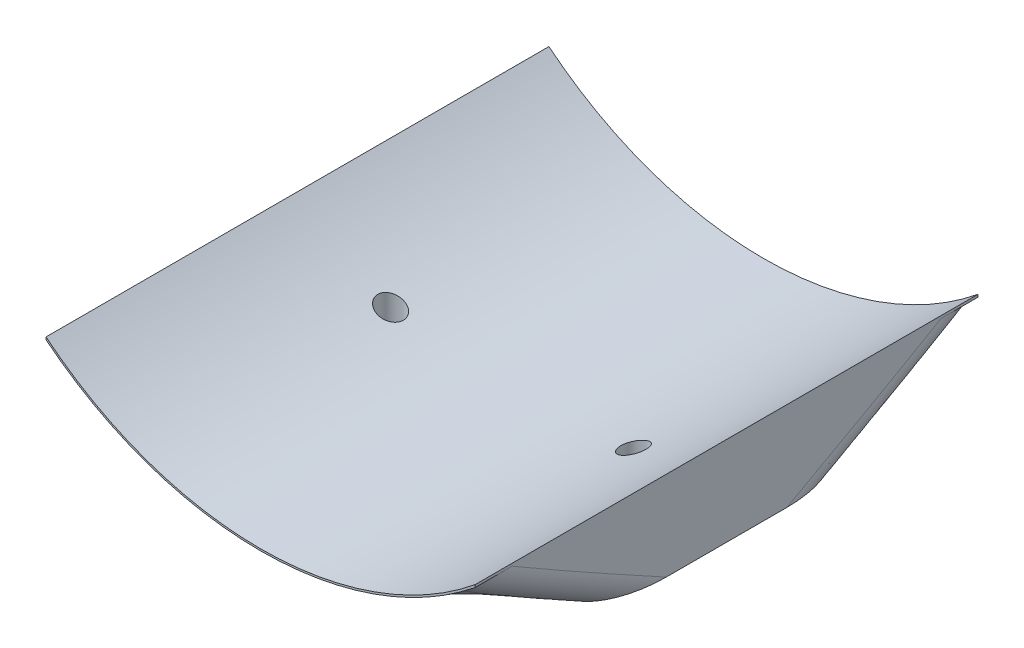
SolidWorks part; units mm, degrees
ref_plane "Front Plane" through (0, 0, 0) normal (0, 0, 1) x (1, 0, 0)
ref_plane "Top Plane" through (0, 0, 0) normal (0, 1, 0) x (1, 0, 0)
ref_plane "Right Plane" through (0, 0, 0) normal (1, 0, 0) x (0, 0, -1)
sketch "Sketch1" plane through (0, 0, 0) normal (0, 0, 1) x (1, 0, 0)
  line L0 (-67.31, 0) -> (0, 0)
  line L1 (0, 0) -> (0, 13.97)
  line L2 (-67.31, 0) -> (-67.31, 13.97)
  arc A0 (-67.31, 13.97) -> (0, 13.97) centre (-33.655, 55.3523) ccw
  dimension "D1" = 53.34
  dimension "D2" = 67.31
  dimension "D3" = 13.97
extrude "Boss-Extrude1" add sketch "Sketch1" along normal blind 40
sketch "Sketch2" plane through (0, 0, 0) normal (0, -1, 0) x (1, 0, 0)
  line L0 (0, 20) -> (-14.605, 20) construction
  line L1 (0, 40) -> (0, 0) construction
  line L2 (-14.605, 20) -> (-52.705, 20) construction
  line L3 (-52.705, 20) -> (-67.31, 20) construction
  line L4 (-67.31, 40) -> (-67.31, 0) construction
  circle A0 centre (-52.705, 20) radius 2
  circle A1 centre (-14.605, 20) radius 2
  dimension "D1" = 4
  dimension "D2" = 38.1
extrude "Cut-Extrude1" cut sketch "Sketch2" against normal through all both and the other way through all
ref_plane "Plane1" through (0, 0, 59.05) normal (0, 0, 1) x (1, 0, 0)
sketch "Sketch3" plane through (0, 0, 59.05) normal (0, 0, 1) x (1, 0, 0)
  line L0 (-67.31, 13.97) -> (-67.31, 0) construction
  line L1 (0, 0) -> (0, 13.97) construction
  line L2 (-67.31, 13.5731) -> (-67.31, 13.97)
  line L3 (0, 13.5731) -> (0, 13.97)
  arc A0 (-67.31, 13.97) -> (0, 13.97) centre (-33.655, 55.3523) ccw
  arc A1 (-67.31, 13.5731) -> (0, 13.5731) centre (-33.655, 55.4658) ccw
  arc A2 (-67.31, 13.97) -> (0, 13.97) centre (-33.655, 55.3523) ccw construction
  dimension "D4" = 53.7369
  dimension "D1" = 0.3969
  dimension "D2" = 0.3969
extrude "Boss-Extrude2" add sketch "Sketch3" along normal blind 0.3969 separate body
loft "Loft2" add section face at (-33.655, 3.9956, 40) section face at (-33.655, 7.8211, 59.05) connector at (-67.31, 0, 40) connector at (-67.31, 13.5731, 59.05)
ref_plane "Plane2" through (0, 0, -19.05) normal (0, 0, -1) x (-1, 0, 0)
sketch "Sketch4" plane through (0, 0, -19.05) normal (0, 0, -1) x (-1, 0, 0)
  line L0 (0, 13.97) -> (0, 13.5731)
  line L1 (0, 0) -> (0, 13.97) construction
  line L2 (67.31, 13.97) -> (67.31, 0) construction
  line L3 (67.31, 13.5731) -> (67.31, 13.97)
  arc A0 (67.31, 13.97) -> (0, 13.97) centre (33.655, 55.3523) cw
  arc A1 (0, 13.5731) -> (67.31, 13.5731) centre (33.655, 55.4658) ccw
  arc A2 (0, 13.97) -> (67.31, 13.97) centre (33.655, 55.3523) ccw construction
  dimension "D1" = 0.3969
  dimension "D3" = 53.7369
  dimension "D2" = 53.34
extrude "Boss-Extrude3" add sketch "Sketch4" along normal blind 0.3969 separate body
loft "Loft3" add section face at (-33.655, 3.9956, 0) section face at (-33.655, 7.8211, -19.05) connector at (-67.31, 0, 0) connector at (-67.31, 13.5731, -19.05)
fillet "Fillet1" radius 5.08 4 edges
equation "\"D2@Sketch3\"=\"D1@Sketch3\""
equation "\"D3@Sketch4\"=\"D2@Sketch4\"+1/64"
equation "\"D4@Sketch3\"=\"D3@Sketch3\"+1/64"
